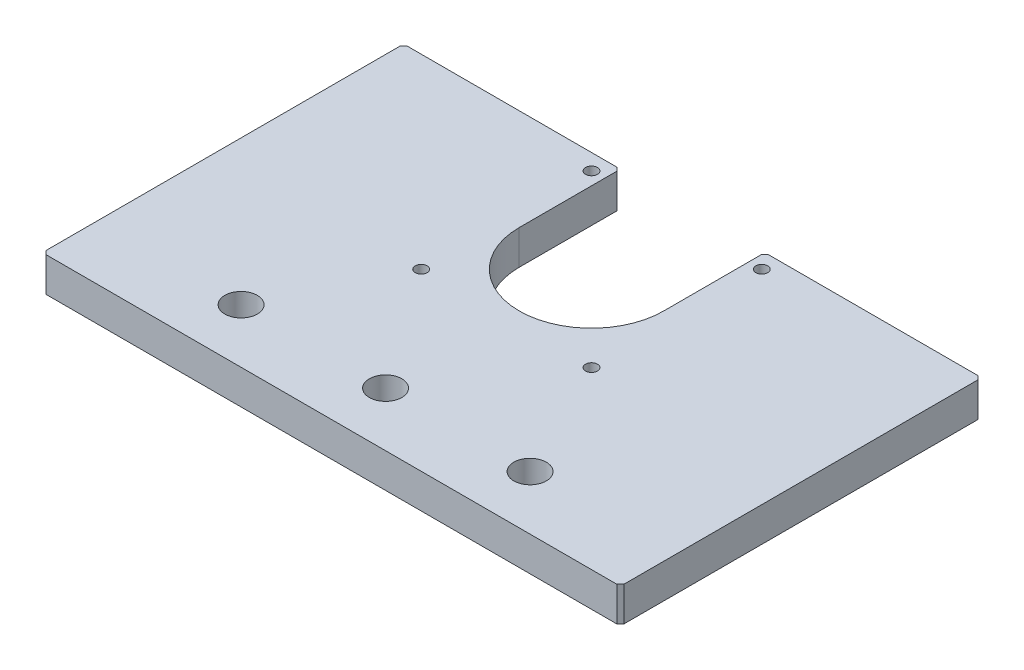
SolidWorks part; units mm, degrees
material "6061-T6 (SS)"
ref_plane "Front Plane" through (0, 0, 0) normal (0, 0, 1) x (1, 0, 0)
ref_plane "Top Plane" through (0, 0, 0) normal (0, 1, 0) x (1, 0, 0)
ref_plane "Right Plane" through (0, 0, 0) normal (1, 0, 0) x (0, 0, -1)
sketch "Sketch1" plane through (0, 0, 0) normal (0, 1, 0) x (1, 0, 0)
  line L0 (20, 0) -> (20, 28)
  line L1 (20, 28) -> (80, 28)
  line L2 (80, 28) -> (80, -72)
  line L3 (80, -72) -> (-80, -72)
  line L4 (-80, -72) -> (-80, 28)
  line L5 (-80, 28) -> (-20, 28)
  line L6 (-20, 28) -> (-20, 0)
  line L7 (-125.0932, -37) -> (-101.7391, -37) construction
  line L8 (-40, -57) -> (0, -57) construction
  line L9 (0, -57) -> (40, -57) construction
  line L10 (0, -55) -> (0, 55) construction
  line L12 (23.5732, 23.5732) -> (-23.5732, 23.5732) construction
  line L13 (23.5732, 23.5732) -> (23.5732, -23.5732) construction
  line L14 (23.5732, -23.5732) -> (-23.5732, -23.5732) construction
  line L15 (-23.5732, 23.5732) -> (-23.5732, -23.5732) construction
  line L16 (23.5732, 23.5732) -> (-23.5732, -23.5732) construction
  line L17 (23.5732, -23.5732) -> (-23.5732, 23.5732) construction
  arc A0 (-20, 0) -> (20, 0) centre (0, 0) ccw
  circle A1 centre (0, 0) radius 33.3375 construction
  dimension "D1" = 20
  dimension "D7" = 66.675
  dimension "D2" = 37
  dimension "D3" = 40
  dimension "D4" = 20
  dimension "D5" = 100
  dimension "D6" = 65
  dimension "D8" = 15
  dimension "D9" = 160
extrude "Boss-Extrude1" add sketch "Sketch1" along normal mid plane 9.525
hole_wizard "M8 Clearance Hole1" positions "Sketch2" profile "Sketch3" hole size "M8" standard "ANSI Metric" end condition through all
sketch "Sketch2" plane through (0, 4.7625, 0) normal (0, 1, 0) x (1, 0, 0)
  point P0 (-40, -57)
  point P3 (0, -57)
  point P6 (40, -57)
sketch "Sketch3" plane through (-40, 4.7625, 57) normal (1, 0, 0) x (0, 0, 1)
  line L0 (0, 0) -> (0, 9.525)
  line L1 (0, 9.525) -> (4.5, 9.525)
  line L2 (4.5, 9.525) -> (4.5, 0)
  line L5 (4.5, 0) -> (0, 0)
  line L11 (0, -6.35) -> (0, 107.95) construction
  dimension "Thru Hole Dia." = 9
  dimension "Thru Hole Depth" = 9.525
hole_wizard "M4x0.7 Tapped Hole2" positions "Sketch4" profile "Sketch5" tap size "M4x0.7" standard "ANSI Metric" end condition up to next
sketch "Sketch4" plane through (0, 4.7625, 0) normal (0, 1, 0) x (1, 0, 0)
  point P0 (-23.5732, -23.5732)
  point P3 (-23.5732, 23.5732)
  point P6 (23.5732, 23.5732)
  point P9 (23.5732, -23.5732)
sketch "Sketch5" plane through (-23.5732, 4.7625, 23.5732) normal (1, 0, 0) x (0, 0, 1)
  line L0 (0, 0) -> (0, 9.525)
  line L1 (0, 9.525) -> (1.65, 9.525)
  line L2 (1.65, 9.525) -> (1.65, 0)
  line L5 (1.65, 0) -> (0, 0)
  line L11 (0, -6.35) -> (0, 107.95) construction
  dimension "Thru Tap Drill Dia." = 3.3
  dimension "Thru Tap Drill Depth" = 9.525
cosmetic thread "Hole Thread1" parameters "D2"=4
cosmetic thread "Hole Thread2" parameters "D2"=4
cosmetic thread "Hole Thread3" parameters "D2"=4
cosmetic thread "Hole Thread4" parameters "D2"=4
chamfer "Chamfer1" distance 1 6 edges at (-80, 0, -28) (-80, 0, 72) (80, 0, 72) (80, 0, -28) (-20, 0, -28) (20, 0, -28)
